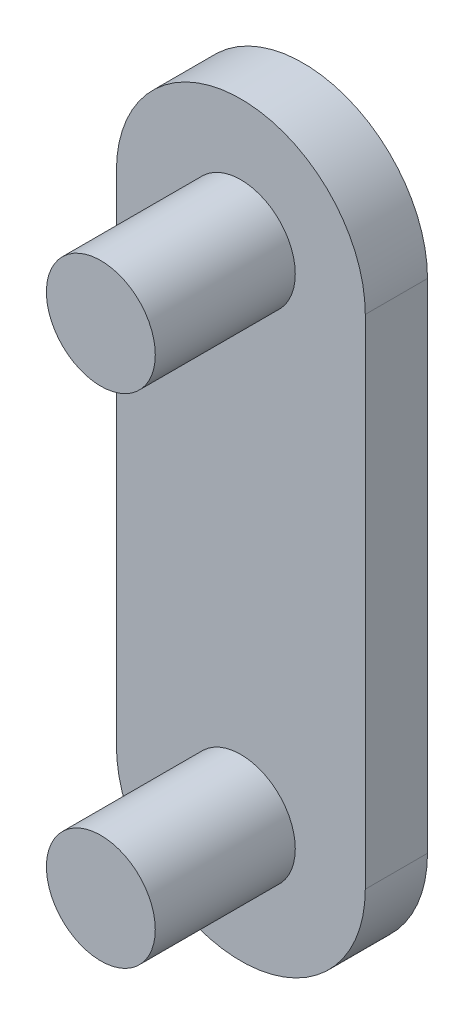
SolidWorks part; units mm, degrees
ref_plane "Front Plane" through (0, 0, 0) normal (0, 0, 1) x (1, 0, 0)
ref_plane "Top Plane" through (0, 0, 0) normal (0, 1, 0) x (1, 0, 0)
ref_plane "Right Plane" through (0, 0, 0) normal (1, 0, 0) x (0, 0, -1)
sketch "Sketch1" plane through (0, 0, 0) normal (0, 0, 1) x (1, 0, 0)
  line L0 (0, 0) -> (0, -16) construction
  line L1 (-4, 0) -> (-4, -16)
  line L2 (4, 0) -> (4, -16)
  circle A0 centre (0, 0) radius 4
  circle A1 centre (0, -16) radius 4
  circle A2 centre (0, 0) radius 1.75
  circle A3 centre (0, -16) radius 1.75
  dimension "D1" = 8
  dimension "D3" = 8
  dimension "D4" = 3.5
  dimension "D5" = 3.5
  dimension "D2" = 16
extrude "Boss-Extrude1" add sketch "Sketch1" against normal blind 2 contours A0 L0 A1 L2 | L0 A0 L1 A1 | A1 A3 | A3 | A0 region at (2.1955, -8, 0) region at (-2.1955, -8, 0) region at (1.2024, -14.7976, 0) region at (2.7484, -13.2516, 0)
extrude "Boss-Extrude2" add sketch "Sketch1<4>" along normal blind 4.5 contours A2 | A3 region at (0, 0, 0) region at (0, -16, 0)
sketch "Sketch1<4>" plane through (0, 0, 0) normal (0, 0, 1) x (1, 0, 0) same geometry as "Sketch1"
